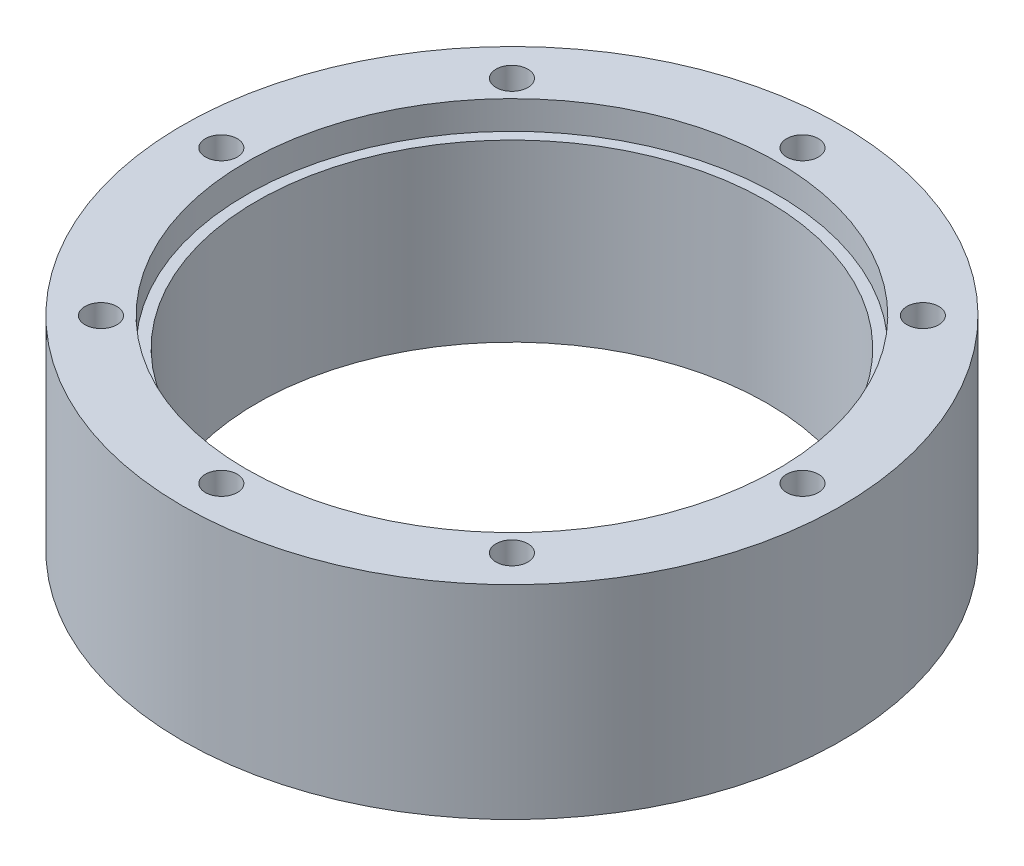
SolidWorks part; units mm, degrees
ref_plane "Front Plane" through (0, 0, 0) normal (0, 0, 1) x (1, 0, 0)
ref_plane "Top Plane" through (0, 0, 0) normal (0, 1, 0) x (1, 0, 0)
ref_plane "Right Plane" through (0, 0, 0) normal (1, 0, 0) x (0, 0, -1)
sketch "Sketch1" plane through (0, 0, 0) normal (0, 1, 0) x (1, 0, 0)
  circle A0 centre (0, 0) radius 46.5
  circle A1 centre (0, 0) radius 36
  dimension "D1" = 93
  dimension "D2" = 72
extrude "Boss-Extrude1" add sketch "Sketch1" along normal blind 28.7
sketch "Sketch2" plane through (0, 28.7, 0) normal (0, 1, 0) x (1, 0, 0)
  circle A0 centre (0, 0) radius 41 construction
  circle A1 centre (0, 41) radius 2.25
  circle A2 centre (28.9914, 28.9914) radius 2.25
  circle A3 centre (41, 0) radius 2.25
  circle A4 centre (28.9914, -28.9914) radius 2.25
  circle A5 centre (0, -41) radius 2.25
  circle A6 centre (-28.9914, -28.9914) radius 2.25
  circle A7 centre (-41, 0) radius 2.25
  circle A8 centre (-28.9914, 28.9914) radius 2.25
  point P22 (0, 0)
  dimension "D1" = 82
  dimension "D2" = 4.5
  dimension "D3" = 8
extrude "Cut-Extrude1" cut sketch "Sketch2" against normal through all
sketch "Sketch3" plane through (0, 28.7, 0) normal (0, 1, 0) x (1, 0, 0)
  circle A0 centre (0, 0) radius 36 construction
  circle A1 centre (0, 0) radius 36
  circle A2 centre (0, 0) radius 37.5
  dimension "D1" = 1.5
extrude "Cut-Extrude2" cut sketch "Sketch3" against normal blind 4
